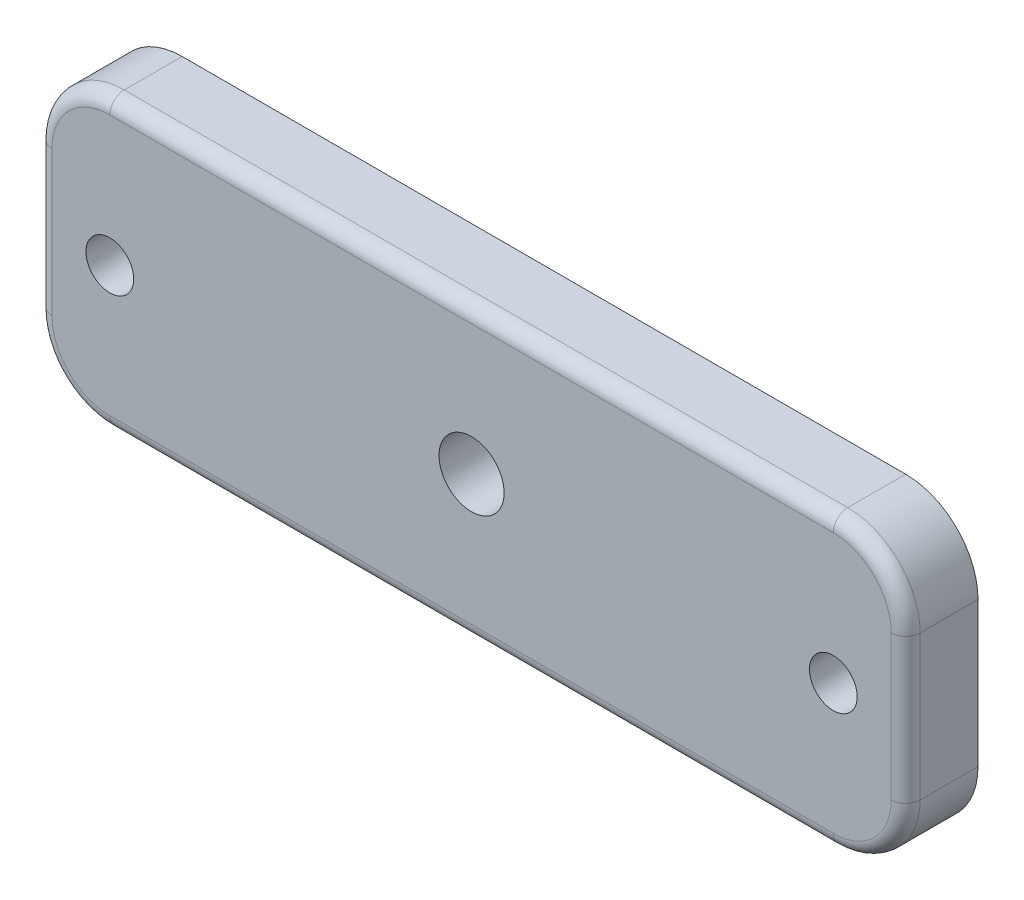
SolidWorks part; units mm, degrees
ref_plane "Plan de face" through (0, 0, 0) normal (0, 0, 1) x (1, 0, 0)
ref_plane "Plan de dessus" through (0, 0, 0) normal (0, 1, 0) x (1, 0, 0)
ref_plane "Plan de droite" through (0, 0, 0) normal (1, 0, 0) x (0, 0, -1)
sketch "Esquisse1" plane through (0, 0, 0) normal (0, 0, 1) x (1, 0, 0)
  line L0 (-30, 0) -> (30, 0)
  line L1 (-30, 0) -> (-30, -20)
  line L2 (-30, -20) -> (30, -20)
  line L3 (30, -20) -> (30, 0)
  circle A0 centre (0, -10) radius 2.25
  circle A1 centre (25, -10) radius 1.65
  circle A2 centre (-25, -10) radius 1.65
  point P4 (0, 0)
  dimension "D3" = 4.5
  dimension "D7" = 3.3
  dimension "D8" = 3.3
  dimension "D1" = 60
  dimension "D2" = 20
  dimension "D4" = 10
  dimension "D5" = 5
  dimension "D6" = 5
extrude "Boss.-Extru.1" add sketch "Esquisse1" along normal blind 5
fillet "Congé1" radius 1 4 edges at (0, -20, 5) (-30, -10, 5) (0, 0, 5) (30, -10, 5)
fillet "Congé3" radius 5 8 edges at (29.7071, -0.2929, 4.7071) (29.7071, -19.7071, 4.7071) (-29.7071, -19.7071, 4.7071) (-29.7071, -0.2929, 4.7071) (-30, 0, 2) (-30, -20, 2) (30, -20, 2) (30, 0, 2)
